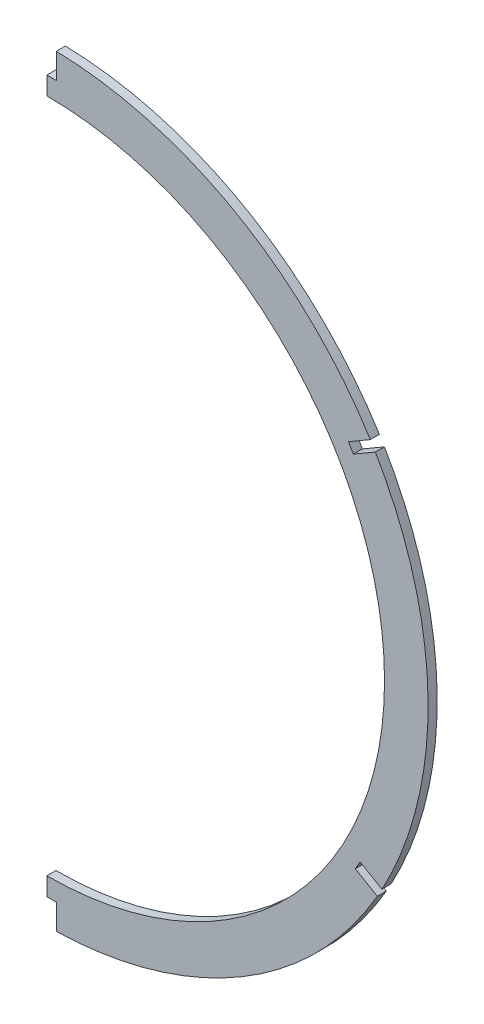
SolidWorks part; units mm, degrees
material "Balsa"
ref_plane "Front Plane" through (0, 0, 0) normal (0, 0, 1) x (1, 0, 0)
ref_plane "Top Plane" through (0, 0, 0) normal (0, 1, 0) x (1, 0, 0)
ref_plane "Right Plane" through (0, 0, 0) normal (1, 0, 0) x (0, 0, -1)
sketch "Sketch1" plane through (0, 0, 0) normal (0, 0, 1) x (1, 0, 0)
  line L0 (0, -110.0909) -> (0, -70.6286) construction
  line L1 (0, 0) -> (0, 245.1538) construction
  line L2 (0, 0) -> (0, 631.6453) construction
  line L3 (-120.188, -34.2725) -> (-93.2472, -61.2132)
  line L4 (0, 0) -> (-284.8905, 0) construction
  line L5 (-93.2472, -61.2132) -> (-94.2927, -70.7977)
  line L8 (-93.2472, -61.2132) -> (-57.7675, -96.693) construction
  arc A0 (-57.7675, -96.693) -> (-120.188, -34.2725) centre (0, 23.495) ccw
  arc A2 (-120.188, -34.2725) -> (-57.7675, -96.693) centre (0, 23.495) ccw construction
  arc A3 (-94.2927, -70.7977) -> (-57.7675, -96.693) centre (0, 23.495) ccw
  point P2 (0, 156.7839)
  point P3 (0, -109.8059)
  point P15 (-93.2472, -61.2132)
  dimension "D1" = 266.5898
  dimension "D2" = 266.7
  dimension "D3" = 23.495
  dimension "D5" = 109.22
  dimension "D6" = 45
  dimension "D7" = 38.1
extrude "Boss-Extrude1" add sketch "Sketch1" along normal mid plane 3.175
sketch "Sketch2" plane through (0, 0, 1.5875) normal (0, 0, 1) x (1, 0, 0)
  line L4 (-77.3048, -55.603) -> (-78.3203, -64.9126)
  line L5 (-107.5191, -25.3887) -> (-77.3048, -55.603)
  line L6 (-77.3048, -55.603) -> (-78.3203, -64.9126)
  line L7 (-107.5191, -25.3887) -> (-77.3048, -55.603)
  arc A2 (-78.3203, -64.9126) -> (-107.5191, -25.3887) centre (0, 23.495) ccw
  arc A3 (-78.3203, -64.9126) -> (-107.5191, -25.3887) centre (0, 23.495) ccw
  dimension "D1" = 15.24
extrude "Cut-Extrude1" cut sketch "Sketch2" against normal up to surface (3.175 mm away) up to face at (-30.5678, -4.3762, -1.5875)
fillet "Fillet1" radius 8.89 6 edges at (-107.5191, -25.3887, 0) (-120.188, -34.2725, 0) (-94.2927, -70.7977, 0) (-93.2472, -61.2132, 0) (-77.3048, -55.603, 0) (-78.3203, -64.9126, 0)
sketch "Sketch3" plane through (0, 0, 0) normal (1, 0, 0) x (0, 0, -1)
  line L1 (-107.0531, 227.715) -> (127.3903, 227.715)
  line L2 (-107.0531, 227.715) -> (-107.0531, -194.8481)
  line L3 (-107.0531, -194.8481) -> (127.3903, -194.8481)
  line L4 (127.3903, 227.715) -> (127.3903, -194.8481)
extrude "Cut-Extrude2" cut sketch "Sketch3" against normal through all
sketch "Sketch4" plane through (0, 0, -1.5875) normal (0, 0, -1) x (-1, 0, 0)
  line L0 (0, 0) -> (0, 141.605) construction
  line L1 (0, 141.605) -> (0, 147.955) construction
  line L2 (-3.302, 147.955) -> (3.302, 147.955)
  line L3 (0, 147.955) -> (0, 160.655)
  line L4 (3.302, 147.955) -> (3.302, 160.655)
  line L5 (-3.302, 160.655) -> (3.302, 160.655)
  line L6 (100.8525, 84.9665) -> (106.3397, 88.1623) construction
  line L7 (105.4896, 89.6219) -> (107.1898, 86.7027)
  line L8 (100.8525, 84.9665) -> (0, 26.2278) construction
  line L9 (105.4896, 89.6219) -> (116.464, 96.0136)
  line L10 (107.1898, 86.7027) -> (118.1641, 93.0944)
  line L11 (116.464, 96.0136) -> (118.1641, 93.0944)
  line L12 (100.5646, -32.3432) -> (108.7167, -37.0911) construction
  line L13 (0, 26.2278) -> (100.5646, -32.3432) construction
  line L14 (107.8666, -38.5507) -> (109.5668, -35.6316)
  line L15 (107.8666, -38.5507) -> (117.8184, -44.3469)
  line L16 (109.5668, -35.6316) -> (119.5186, -41.4277)
  line L17 (117.8184, -44.3469) -> (119.5186, -41.4277)
  line L18 (0, 26.2278) -> (0, -94.615) construction
  line L19 (0, -94.615) -> (0, -100.965) construction
  line L20 (-3.302, -100.965) -> (3.302, -100.965)
  line L21 (0, -100.965) -> (0, -113.665)
  line L22 (3.302, -100.965) -> (3.302, -113.665)
  line L23 (-3.302, -113.665) -> (3.302, -113.665)
  line L24 (0, 26.2278) -> (-100.5646, -32.3432) construction
  line L25 (-100.5646, -32.3432) -> (-108.7167, -37.0911) construction
  line L26 (-100.8525, 84.9665) -> (0, 26.2278) construction
  line L27 (-100.8525, 84.9665) -> (-106.3397, 88.1623) construction
  line L28 (-3.302, -100.965) -> (-3.302, -113.665)
  line L29 (-117.8184, -44.3469) -> (-119.5186, -41.4277)
  line L30 (-109.5668, -35.6316) -> (-119.5186, -41.4277)
  line L31 (-107.8666, -38.5507) -> (-117.8184, -44.3469)
  line L32 (-107.8666, -38.5507) -> (-109.5668, -35.6316)
  line L33 (-116.464, 96.0136) -> (-118.1641, 93.0944)
  line L34 (-107.1898, 86.7027) -> (-118.1641, 93.0944)
  line L35 (-105.4896, 89.6219) -> (-116.464, 96.0136)
  line L36 (-105.4896, 89.6219) -> (-107.1898, 86.7027)
  line L37 (-3.302, 147.955) -> (-3.302, 160.655)
  point P2 (-103.2295, -33.8953)
  point P10 (-103.2295, -33.8953)
  point P39 (108.7167, -37.0911)
  arc M26 (0, 156.845) -> (0, -109.855) centre (0, 23.495) ccw
  line M27 (0, -109.855) -> (0, -94.615)
  line M29 (0, 141.605) -> (0, 156.845)
  dimension "D1" = 26.2278
  dimension "D2" = 59.783
  dimension "D3" = 59.783
  dimension "D4" = 116.711
  dimension "D5" = 6.35
  dimension "D6" = 12.7
  dimension "D7" = 3.3782
  dimension "D8" = 141.605
  dimension "D9" = 6.35
  dimension "D10" = 3.302
  dimension "D11" = 12.7
  dimension "D12" = 6.35
  dimension "D13" = 120.8428
  dimension "D14" = 3.302
  dimension "D15" = 12.7
  dimension "D16" = 116.3778
  dimension "D17" = 119.4618
  dimension "D18" = 6.35
  dimension "D19" = 3.3782
extrude "Cut-Extrude3" cut sketch "Sketch4" against normal through all contours L37 L2 M29 M26 | L36 L35 L34 M26 | L31 L32 L30 M26 | L20 L28 M26 M27 region at (1.6497, 152.3932, -1.5875) region at (1.6497, -105.4032, -1.5875) region at (112.5564, -39.3297, -1.5875) region at (110.1813, 90.3975, -1.5875)
